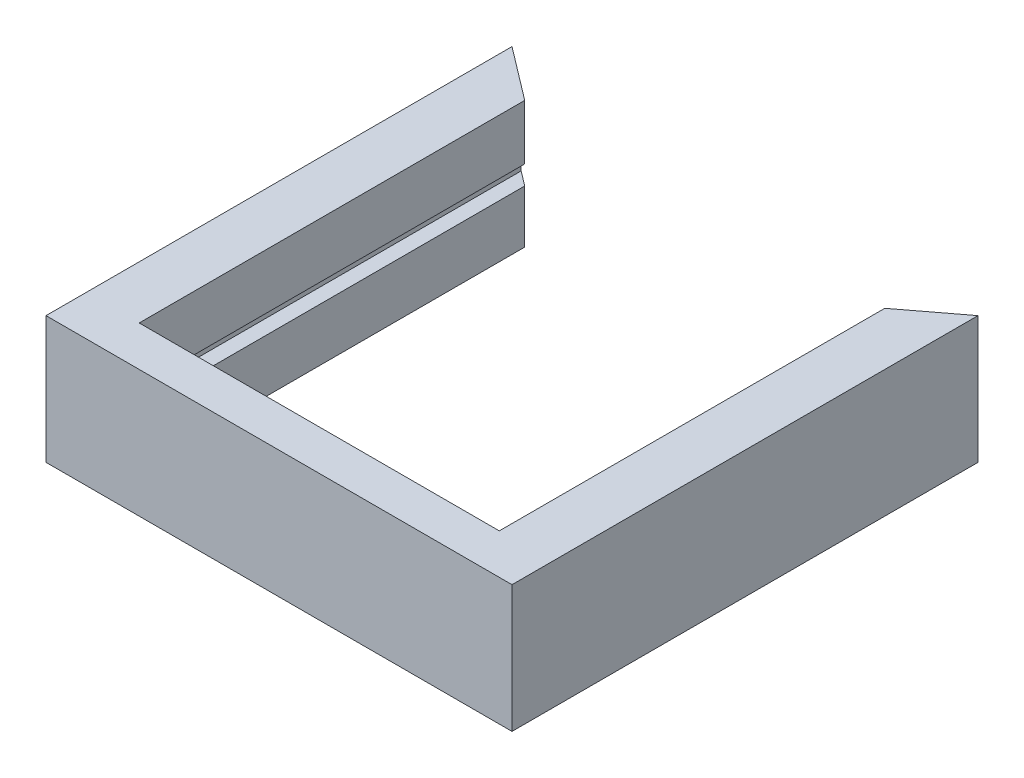
SolidWorks part; units mm, degrees
ref_plane "Front Plane" through (0, 0, 0) normal (0, 0, 1) x (1, 0, 0)
ref_plane "Top Plane" through (0, 0, 0) normal (0, 1, 0) x (1, 0, 0)
ref_plane "Right Plane" through (0, 0, 0) normal (1, 0, 0) x (0, 0, -1)
sketch "Sketch1" plane through (0, 0, 0) normal (0, 1, 0) x (1, 0, 0)
  line L0 (-55, 55) -> (-42.5, 45.5)
  line L1 (-42.5, -45.5) -> (42.5, -45.5)
  line L2 (-42.5, -45.5) -> (-42.5, 45.5)
  line L4 (42.5, -45.5) -> (42.5, 45.5)
  line L5 (-42.5, -45.5) -> (42.5, 45.5) construction
  line L6 (-42.5, 45.5) -> (42.5, -45.5) construction
  line L7 (-55, -55) -> (55, -55)
  line L8 (-55, -55) -> (-55, 55)
  line L10 (55, -55) -> (55, 55)
  line L11 (-55, -55) -> (55, 55) construction
  line L12 (-55, 55) -> (55, -55) construction
  line L13 (55, 55) -> (42.5, 45.5)
  point P0 (0, 0)
  point P6 (0, 0)
  dimension "D1" = 85
  dimension "D2" = 91
  dimension "D3" = 110
  dimension "D4" = 110
extrude "Boss-Extrude1" add sketch "Sketch1" along normal blind 30
sketch "Sketch2" plane through (0, 0, 45.5) normal (0, 0, -1) x (-1, 0, 0)
  line L0 (-42.5, 0) -> (42.5, 0) construction
  line L1 (-46, 12.5) -> (46, 12.5)
  line L2 (-46, 12.5) -> (-46, 17.5)
  line L3 (-46, 17.5) -> (46, 17.5)
  line L4 (46, 12.5) -> (46, 17.5)
  line L5 (-46, 12.5) -> (46, 17.5) construction
  line L6 (-46, 17.5) -> (46, 12.5) construction
  point P0 (0, 15)
  point P7 (0, 0)
  dimension "D1" = 92
  dimension "D2" = 0
  dimension "D3" = 5
  dimension "D4" = 15
extrude "Cut-Extrude1" cut sketch "Sketch2" along normal through all
chamfer "Chamfer1" distance 4 angle 45 2 edges at (-46, 17.5, -1.33) (46, 17.5, -1.33)
